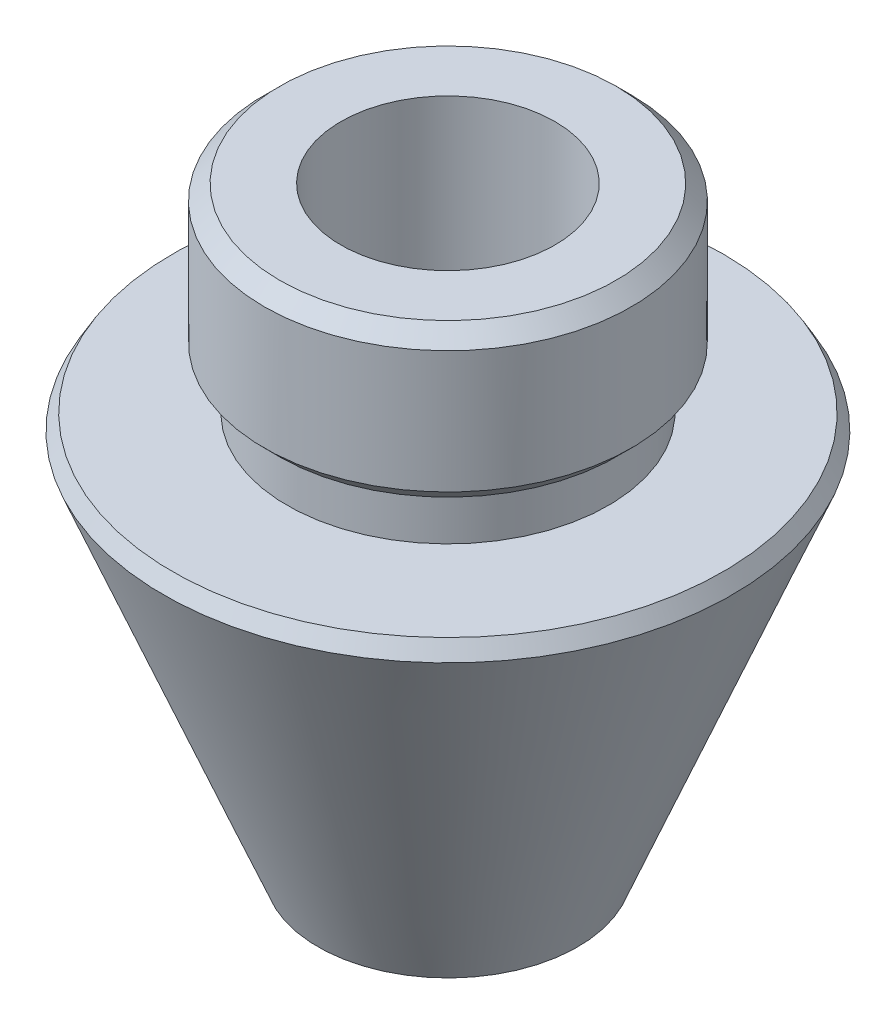
SolidWorks part; units mm, degrees
material "Cobre"
ref_plane "Plano frontal" through (0, 0, 0) normal (0, 0, 1) x (1, 0, 0)
ref_plane "Plano superior" through (0, 0, 0) normal (0, 1, 0) x (1, 0, 0)
ref_plane "Plano direito" through (0, 0, 0) normal (1, 0, 0) x (0, 0, -1)
sketch "Esboço1" plane through (0, 0, 0) normal (1, 0, 0) x (0, 0, -1)
  line L0 (0, 0) -> (0, 40) construction
  line L1 (10.5, 18.7681) -> (19, 18.7681)
  line L2 (19, 18.7681) -> (8.4953, -7.2319)
  line L3 (8.4953, -7.2319) -> (7, -7.2319)
  line L4 (7, 31.7681) -> (7, -7.2319)
  line L5 (-0.5769, 0) -> (1.7552, 0)
  line L6 (10.5, 18.7681) -> (10.5, 21.7681)
  line L7 (10.5, 21.7681) -> (12, 21.7681)
  line L8 (12, 21.7681) -> (12, 31.7681)
  line L9 (12, 31.7681) -> (7, 31.7681)
  line L10 (18, 18.7681) -> (18.5883, 17.7491)
  point P14 (0, 20)
  dimension "D1" = 26
  dimension "D2" = 7
  dimension "D3" = 38
  dimension "D4" = 24
  dimension "D5" = 3
  dimension "D6" = 10
  dimension "D7" = 21
  dimension "D8" = 68
  dimension "D9" = 1
  dimension "D10" = 60
revolve "Revolução1" add sketch "Esboço1" angle 360 about L0 region at (0, 13.3609, -10.6059)
cosmetic thread "Representação de rosca1" parameters "D2"=21.797
chamfer "Chanfro1" distance 1 angle 45 1 edges at (0, 31.7681, -12)
chamfer "Chanfro2" distance 1 angle 45 1 edges at (0, 21.7681, -12)
fillet "Filete1" radius 10 1 edges at (0, -7.2319, -7)
